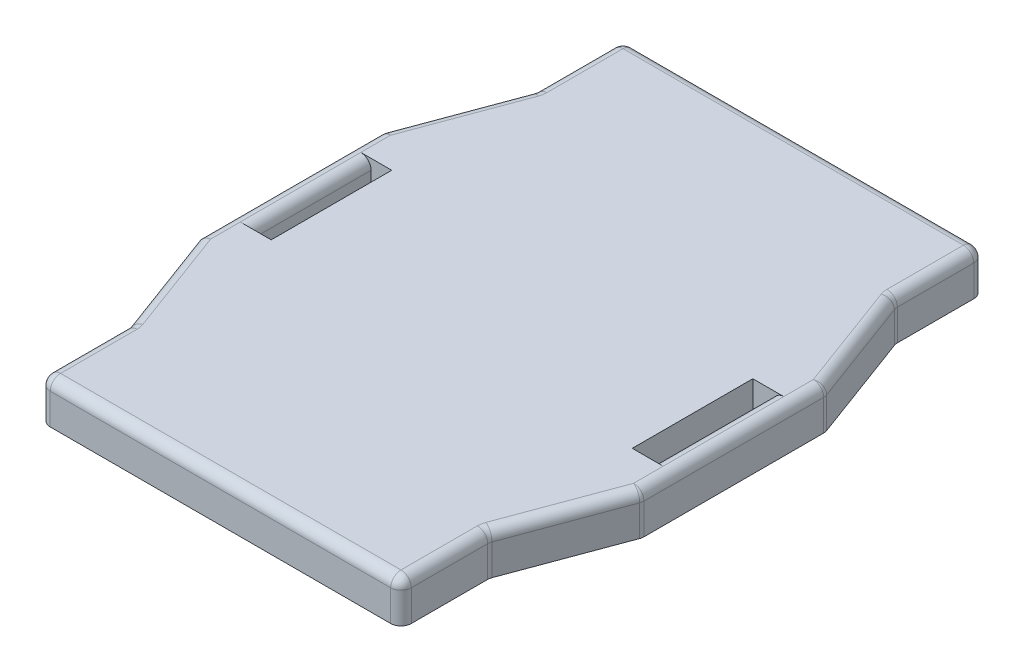
SolidWorks part; units mm, degrees
note: The reader was unsure of these and kept them because the rebuilt part matched: shared geometry of "Sketch1<3>".
material "ABS"
ref_plane "Front Plane" through (0, 0, 0) normal (0, 0, 1) x (1, 0, 0)
ref_plane "Top Plane" through (0, 0, 0) normal (0, 1, 0) x (1, 0, 0)
ref_plane "Right Plane" through (0, 0, 0) normal (1, 0, 0) x (0, 0, -1)
sketch "Sketch1" plane through (0, 0, 0) normal (0, 1, 0) x (1, 0, 0)
  line L0 (43.75, 70.65) -> (-43.75, 70.65)
  line L1 (37.75, 64.65) -> (-37.75, 64.65)
  line L2 (37.75, 64.65) -> (37.75, -64.65)
  line L3 (37.75, -64.65) -> (-37.75, -64.65)
  line L4 (-37.75, 64.65) -> (-37.75, -64.65)
  line L5 (37.75, 64.65) -> (-37.75, -64.65) construction
  line L6 (37.75, -64.65) -> (-37.75, 64.65) construction
  line L7 (-43.75, 70.65) -> (-43.75, -70.65)
  line L8 (43.75, -70.65) -> (-43.75, -70.65)
  line L9 (43.75, 70.65) -> (43.75, -70.65)
  point P0 (0, 0)
  dimension "D1" = 75.5
  dimension "D2" = 129.3
  dimension "D3" = 6
extrude "Boss-Extrude1" add sketch "Sketch1" along normal blind 4 contours L7 L8 L9 L0
extrude "Boss-Extrude2" add sketch "Sketch1<3>" against normal blind 6
sketch "Sketch1<3>" plane through (0, 0, 0) normal (0, 1, 0) x (1, 0, 0) same geometry as "Sketch1"
sketch "Sketch2" plane through (0, 4, 0) normal (0, 1, 0) x (1, 0, 0)
  line L0 (0, 0) -> (-72.118, 0) construction
  line L1 (0, 0) -> (0, -41.3244) construction
  line L2 (-43.75, 70.65) -> (-43.75, -70.65) construction
  line L3 (-53.75, 22.225) -> (-43.75, 22.225) construction
  line L4 (-53.75, 22.225) -> (-53.75, -22.225)
  line L5 (-53.75, -22.225) -> (-43.75, -22.225) construction
  line L6 (-43.75, 22.225) -> (-43.75, 0)
  line L7 (-53.75, 22.225) -> (-43.75, -22.225) construction
  line L8 (-53.75, -22.225) -> (-43.75, 22.225) construction
  line L9 (43.75, 22.225) -> (43.75, 14.605)
  line L10 (-48.75, -14.605) -> (-43.75, -14.605)
  line L11 (-48.75, -14.605) -> (-48.75, 14.605)
  line L12 (-48.75, 14.605) -> (-43.75, 14.605)
  line L13 (-43.75, 0) -> (-43.75, 14.605)
  line L14 (-48.75, -14.605) -> (-43.75, 14.605) construction
  line L15 (-48.75, 14.605) -> (-43.75, -14.605) construction
  line L16 (53.75, 22.225) -> (43.75, 22.225)
  line L17 (48.75, 14.605) -> (43.75, 14.605)
  line L18 (48.75, -14.605) -> (43.75, -14.605)
  line L19 (53.75, -22.225) -> (43.75, -22.225) construction
  line L20 (48.75, -14.605) -> (48.75, 14.605)
  line L21 (53.75, 22.225) -> (53.75, -22.225)
  line L22 (-43.75, -14.605) -> (-43.75, -22.225)
  line L23 (43.75, -14.605) -> (43.75, -22.225)
  line L24 (-53.75, -22.225) -> (-43.75, -49.1886)
  line L25 (-43.75, -49.1886) -> (-43.75, -22.225)
  line L26 (-53.75, 22.225) -> (-43.75, 49.1886)
  line L27 (-43.75, 49.1886) -> (-43.75, 22.225)
  line L28 (53.75, 22.225) -> (43.75, 49.1886)
  line L29 (43.75, 70.65) -> (43.75, -70.65) construction
  line L30 (53.75, -22.225) -> (43.75, -49.1886)
  line L31 (43.75, 49.1886) -> (43.75, 22.225)
  line L32 (43.75, -49.1886) -> (43.75, -22.225)
  line L33 (-43.75, -49.1886) -> (-43.75, -22.225)
  point P3 (-48.75, 0)
  point P11 (-46.25, 0)
  line M4 (-43.75, 70.65) -> (-43.75, -70.65)
  dimension "D1" = 29.21
  dimension "D2" = 44.45
  dimension "D3" = 10
  dimension "D4" = 5
extrude "Boss-Extrude3" add sketch "Sketch2" against normal up to vertex (10 mm away) contours L11 L12 L3 L4 L5 L10 M4 | L21 L30 L32 L23 L18 L20 L17 L9 L31 L28
fillet "Fillet2" radius 2.5 25 edges at (0, 4, 70.65) (43.75, 4, -59.9193) (-43.75, 4, 59.9193) (0, 4, -70.65) (-48.75, 4, -35.7068) (-53.75, -1, -22.225) (-43.75, -1, -49.1886) (-43.75, -1, 49.1886) (-53.75, 4, 0) (-48.75, 4, 35.7068) (-48.75, 4, 0) (43.75, 4, 59.9193) (43.75, -1, -49.1886) (53.75, 4, 0) (53.75, -1, -22.225) (48.75, 4, 35.7068) (53.75, -1, 22.225) (43.75, -1, 49.1886) (48.75, 4, 0) (-43.75, 4, -59.9193) (48.75, 4, -35.7068) (43.75, -1, -70.65) (43.75, -1, 70.65) (-43.75, -1, 70.65) (-43.75, -1, -70.65)
